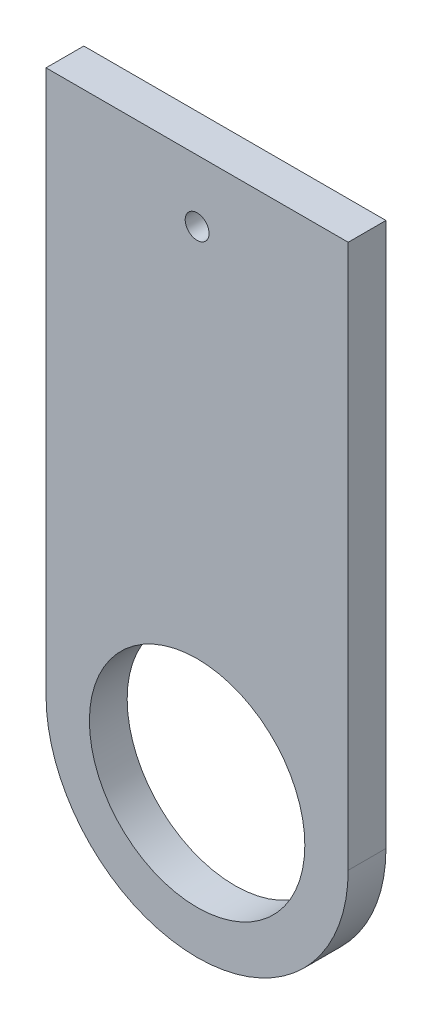
SolidWorks part; units mm, degrees
ref_plane "Front Plane" through (0, 0, 0) normal (0, 0, 1) x (1, 0, 0)
ref_plane "Top Plane" through (0, 0, 0) normal (0, 1, 0) x (1, 0, 0)
ref_plane "Right Plane" through (0, 0, 0) normal (1, 0, 0) x (0, 0, -1)
sketch "Sketch1" plane through (0, 0, 0) normal (0, 0, 1) x (1, 0, 0)
  line L0 (0, 78.0535) -> (0, -76.7078) construction
  line L1 (-108.1983, 0.6729) -> (119.7718, 0.6729) construction
  line L2 (-12.0732, -76.7078) -> (17.2347, -76.7078) construction
  line L3 (-20, -76.7078) -> (-20, -58.5041)
  line L4 (-20, -4.7078) -> (20, -4.7078)
  line L5 (20, -4.7078) -> (20, -76.7078)
  line L9 (-20, -4.7078) -> (-20, -58.5041)
  line L10 (-38, -22.9117) -> (-38, -2.9117) construction
  arc A0 (-20, -76.7078) -> (20, -76.7078) centre (0, -76.7078) ccw
  circle A3 centre (0, -12.9117) radius 1.58
  circle A4 centre (0, -76.7078) radius 14.26
  dimension "D1" = 40
  dimension "D4" = 20
  dimension "D5" = 3.16
  dimension "D2" = 40
  dimension "D3" = 72
extrude "Boss-Extrude1" add sketch "Sketch1" along normal blind 5
sketch "Sketch5" plane through (0, 0, 0) normal (0, 0, 1) x (1, 0, 0)
  line L0 (-48.8454, -50.3255) -> (64.5713, -50.3255) construction
  line L1 (0, 12.932) -> (0, -107.7413) construction
